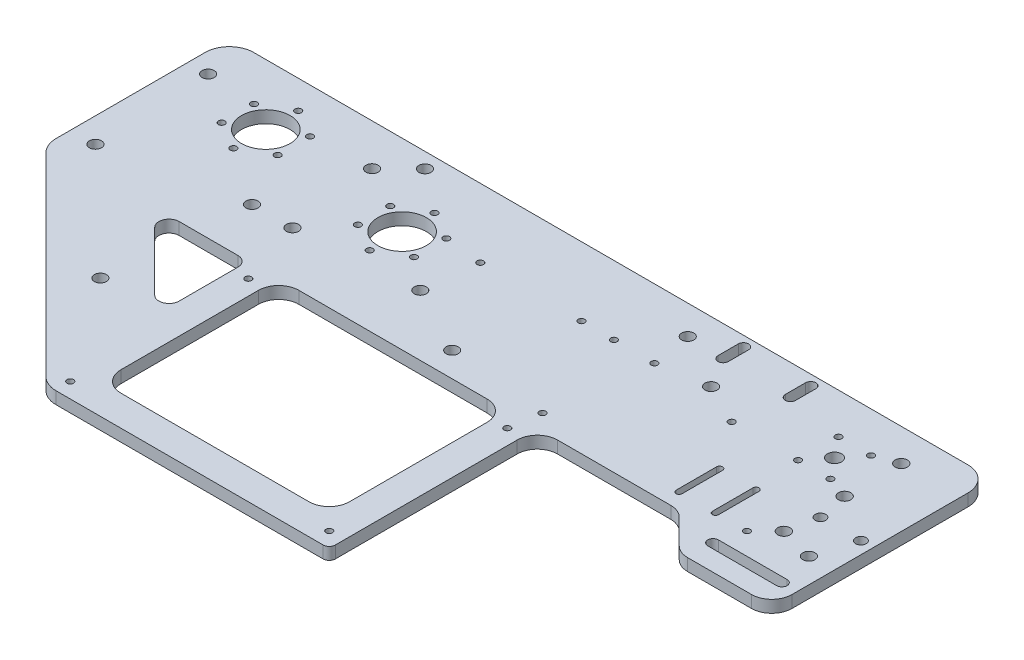
SolidWorks part; units mm, degrees
material "Policarbonato"
ref_plane "Plano frontal" through (0, 0, 0) normal (0, 0, 1) x (1, 0, 0)
ref_plane "Plano superior" through (0, 0, 0) normal (0, 1, 0) x (1, 0, 0)
ref_plane "Plano direito" through (0, 0, 0) normal (1, 0, 0) x (0, 0, -1)
sketch "Esboço1" plane through (0, 0, 0) normal (0, 1, 0) x (1, 0, 0)
  line L3 (-80.5574, -153.6487) -> (51.4721, -153.6487)
  line L4 (54.4721, -150.6487) -> (54.4721, -60.7886)
  line L6 (188.5279, -40.7886) -> (188.5279, 28)
  line L7 (176.5279, 40) -> (-176.5279, 40)
  line L8 (-188.5279, 28) -> (-188.5279, -45.6781)
  line L12 (-122.5768, -50.7886) -> (-93.5279, -50.7886)
  line L13 (-88.5279, -55.7886) -> (-88.5279, -84.8375)
  line L14 (-97.0635, -88.373) -> (-126.1124, -59.3241)
  line L15 (39.4721, -60.6487) -> (39.4721, -128.6487)
  line L16 (29.4721, -138.6487) -> (-63.5279, -138.6487)
  line L17 (-73.5279, -128.6487) -> (-73.5279, -60.6487)
  line L18 (-63.5279, -50.6487) -> (29.4721, -50.6487)
  line L20 (132.5279, 0) -> (148.5279, 0) construction
  line L21 (132.5279, 0) -> (132.5279, 20) construction
  line L22 (132.5279, 20) -> (148.5279, 20) construction
  line L23 (148.5279, 0) -> (148.5279, 20) construction
  line L24 (132.5279, 0) -> (148.5279, 20) construction
  line L25 (132.5279, 20) -> (148.5279, 0) construction
  line L30 (64.4721, -50.7886) -> (178.5279, -50.7886)
  line L31 (134.7221, -43) -> (134.7221, -23) construction
  line L32 (133.2221, -43) -> (133.2221, -23)
  line L33 (136.2221, -43) -> (136.2221, -23)
  line L34 (125.7221, -45.2211) -> (125.7221, -21.4375) construction
  line L36 (116.7221, -43) -> (116.7221, -23) construction
  line L37 (118.2221, -43) -> (118.2221, -23)
  line L38 (115.2221, -43) -> (115.2221, -23)
  line L40 (54.4721, -120.5) -> (144.9721, -120.5) construction
  line L41 (54.4721, -120.5) -> (54.4721, -7) construction
  line L42 (54.4721, -7) -> (144.9721, -7) construction
  line L43 (144.9721, -120.5) -> (144.9721, -7) construction
  line L44 (54.4721, -120.5) -> (144.9721, -7) construction
  line L45 (54.4721, -7) -> (144.9721, -120.5) construction
  line L46 (70.5279, 25) -> (70.5279, 35) construction
  line L47 (67.9779, 25) -> (67.9779, 35)
  line L48 (73.0779, 25) -> (73.0779, 35)
  line L49 (103.7779, 25) -> (103.7779, 35) construction
  line L50 (101.2279, 25) -> (101.2279, 35)
  line L51 (106.3279, 25) -> (106.3279, 35)
  line L52 (-185.0132, -54.1634) -> (-89.0426, -150.134)
  circle A0 centre (-81.0279, -58.1487) radius 1.6
  circle A1 centre (-81.0279, -146.1487) radius 1.6
  circle A2 centre (46.9721, -58.1487) radius 1.6
  circle A3 centre (46.9721, -146.1487) radius 1.6
  circle A8 centre (176.311, -38.4318) radius 3
  circle A9 centre (0, -38.4318) radius 3
  circle A11 centre (-140.5279, 10) radius 12
  circle A20 centre (-140.5279, 10) radius 16 construction
  circle A21 centre (-140.5279, -6) radius 1.6
  circle A22 centre (-154.3843, 2) radius 1.6
  circle A23 centre (-154.3843, 18) radius 1.6
  circle A24 centre (-84.3674, 32.5) radius 3
  circle A25 centre (-176.311, -38.4318) radius 3
  circle A26 centre (140.5279, 10) radius 3.5
  circle A27 centre (148.5279, 0) radius 1.6
  circle A28 centre (148.5279, 20) radius 1.6
  circle A29 centre (132.5279, 0) radius 1.6
  circle A30 centre (132.5279, 20) radius 1.6
  arc A31 (51.4721, -153.6487) -> (54.4721, -150.6487) centre (51.4721, -150.6487) ccw
  arc A34 (188.5279, 28) -> (176.5279, 40) centre (176.5279, 28) ccw
  arc A35 (-176.5279, 40) -> (-188.5279, 28) centre (-176.5279, 28) ccw
  arc A39 (-93.5279, -50.7886) -> (-88.5279, -55.7886) centre (-93.5279, -55.7886) cw
  arc A40 (-88.5279, -84.8375) -> (-97.0635, -88.373) centre (-93.5279, -84.8375) cw
  arc A41 (-126.1124, -59.3241) -> (-122.5768, -50.7886) centre (-122.5768, -55.7886) cw
  arc A42 (39.4721, -128.6487) -> (29.4721, -138.6487) centre (29.4721, -128.6487) cw
  arc A43 (-63.5279, -138.6487) -> (-73.5279, -128.6487) centre (-63.5279, -128.6487) cw
  arc A44 (-73.5279, -60.6487) -> (-63.5279, -50.6487) centre (-63.5279, -60.6487) cw
  arc A45 (29.4721, -50.6487) -> (39.4721, -60.6487) centre (29.4721, -60.6487) cw
  circle A46 centre (-140.5279, 26) radius 1.6
  circle A47 centre (-126.6715, 18) radius 1.6
  circle A48 centre (-126.6715, 2) radius 1.6
  circle A49 centre (-63.1716, 0) radius 16 construction
  circle A50 centre (-63.1716, -16) radius 1.6
  circle A51 centre (-77.028, -8) radius 1.6
  circle A52 centre (-77.028, 8) radius 1.6
  circle A53 centre (-63.1716, 16) radius 1.6
  circle A54 centre (-49.3152, 8) radius 1.6
  circle A55 centre (-49.3152, -8) radius 1.6
  circle A56 centre (-63.1716, 0) radius 12
  circle A57 centre (-33.5279, -20.6487) radius 3
  circle A58 centre (79.5279, 10) radius 3
  arc A62 (188.5279, -40.7886) -> (178.5279, -50.7886) centre (178.5279, -40.7886) cw
  arc A63 (54.4721, -60.7886) -> (64.4721, -50.7886) centre (64.4721, -60.7886) cw
  arc A64 (133.2221, -43) -> (136.2221, -43) centre (134.7221, -43) ccw
  arc A65 (136.2221, -23) -> (133.2221, -23) centre (134.7221, -23) ccw
  arc A66 (118.2221, -43) -> (115.2221, -43) centre (116.7221, -43) cw
  arc A67 (115.2221, -23) -> (118.2221, -23) centre (116.7221, -23) cw
  circle A68 centre (99.7221, 0) radius 1.6
  circle A69 centre (49.2221, -43) radius 1.6
  circle A70 centre (134.7221, -43) radius 1.6 construction
  circle A71 centre (-30.5279, 6) radius 1.6
  circle A72 centre (19.4721, 6) radius 1.6
  circle A73 centre (55.5279, 6) radius 1.6
  circle A75 centre (35.5279, 6) radius 1.6
  circle A76 centre (70.5279, 30) radius 2.55 construction
  circle A77 centre (103.7779, 30) radius 2.55 construction
  circle A78 centre (159.4679, 24.07) radius 3.05
  circle A79 centre (159.4679, -3.93) radius 3.05
  circle A80 centre (159.4679, -33.93) radius 3.05
  arc A81 (67.9779, 25) -> (73.0779, 25) centre (70.5279, 25) ccw
  arc A82 (73.0779, 35) -> (67.9779, 35) centre (70.5279, 35) ccw
  arc A83 (101.2279, 25) -> (106.3279, 25) centre (103.7779, 25) ccw
  arc A84 (106.3279, 35) -> (101.2279, 35) centre (103.7779, 35) ccw
  circle A85 centre (-178.5279, 19.5) radius 3
  circle A86 centre (-97.5279, 19.5) radius 3
  arc A87 (-80.5574, -153.6487) -> (-89.0426, -150.134) centre (-80.5574, -141.6487) cw
  arc A88 (-185.0132, -54.1634) -> (-188.5279, -45.6781) centre (-176.5279, -45.6781) cw
  circle A89 centre (52.3279, 25.68) radius 3
  circle A90 centre (150.2221, -43) radius 1.6
  point P14 (134.7221, -33)
  point P43 (-140.5279, 10)
  point P70 (-144.4721, -50.6487)
  point P82 (-85.5279, -153.6487)
  point P116 (-63.1716, 0)
  point P123 (0, 40)
  point P124 (116.7221, -33)
  point P129 (99.7221, -63.75)
  point P141 (99.7221, -7)
  point P161 (70.5279, 30)
  point P168 (103.7779, 30)
  dimension "D2" = 3
  dimension "D8" = 12
  dimension "D10" = 12
  dimension "D11" = 61
  dimension "D12" = 203.9448
  dimension "D13" = 7.5
  dimension "D14" = 104.1605
  dimension "D16" = 135.7229
  dimension "D20" = 19.68
  dimension "D21" = 3.2
  dimension "D22" = 48.4318
  dimension "D23" = 32
  dimension "D24" = 3.2
  dimension "D25" = 6
  dimension "D26" = 24
  dimension "D27" = 48
  dimension "D28" = 30
  dimension "D29" = 40
  dimension "D30" = 6
  dimension "D34" = 30
  dimension "D31" = 32
  dimension "D32" = 3.2
  dimension "D33" = 24
  dimension "D35" = 6
  dimension "D36" = 155
  dimension "D37" = 30
  dimension "D44" = 7
  dimension "D48" = 10
  dimension "D54" = 50.5
  dimension "D6" = 10
  dimension "D58" = 5
  dimension "D62" = 1.5
  dimension "D72" = 85
  dimension "D75" = 5.1
  dimension "D80" = 14.07
  dimension "D82" = 6.1
  dimension "D83" = 10
  dimension "D19" = 6
  dimension "D47" = 101
  dimension "D1" = 137
  dimension "D9" = 377.0558
  dimension "D15" = 225
  dimension "D17" = 38
  dimension "D18" = 15
  dimension "D38" = 48
  dimension "D39" = 15
  dimension "D40" = 12.2169
  dimension "D41" = 12.2169
  dimension "D42" = 16
  dimension "D43" = 20
  dimension "D45" = 15
  dimension "D46" = 15
  dimension "D49" = 7.5
  dimension "D50" = 7.5
  dimension "D51" = 88
  dimension "D52" = 128
  dimension "D53" = 93
  dimension "D56" = 20.6487
  dimension "D57" = 68
  dimension "D59" = 10
  dimension "D60" = 20.5
  dimension "D61" = 20
  dimension "D63" = 9
  dimension "D64" = 113.5
  dimension "D65" = 90.5
  dimension "D66" = 7
  dimension "D67" = 43
  dimension "D69" = 34
  dimension "D70" = 110
  dimension "D71" = 50
  dimension "D73" = 20
  dimension "D74" = 33.25
  dimension "D76" = 10
  dimension "D77" = 15
  dimension "D78" = 30
  dimension "D79" = 28
  dimension "D81" = 18.94
  dimension "D84" = 81
extrude "Ressalto-extrusão1" add sketch "Esboço1" against normal blind 6
sketch "Esboço2" plane through (0, 0, 0) normal (0, 1, 0) x (1, 0, 0)
  line L0 (188.5279, -40.7886) -> (188.5279, 28) construction
  line L1 (-126.1124, -59.3241) -> (-97.0635, -88.373) construction
  line L2 (-131.2731, -107.9035) -> (-104.403, -81.0335) construction
  line L3 (-185.0132, -54.1634) -> (-89.0426, -150.134) construction
  line L4 (159.4679, -6.98) -> (159.4679, -30.88) construction
  line L5 (-140.5279, 10) -> (-63.1716, 0) construction
  line L6 (176.5279, 40) -> (-176.5279, 40) construction
  line L7 (-91.8498, -25.5) -> (-111.8498, -25.5) construction
  circle A1 centre (-117.8381, -94.4685) radius 3
  arc A2 (-188.5279, -45.6781) -> (-185.0132, -54.1634) centre (-176.5279, -45.6781) ccw construction
  circle A3 centre (182.5279, -18.93) radius 2.6
  circle A4 centre (162.5279, -18.93) radius 2.6
  circle A7 centre (-111.8498, -25.5) radius 3
  circle A8 centre (-91.8498, -25.5) radius 3
  circle A9 centre (159.4679, -3.93) radius 3.05 construction
  circle A10 centre (159.4679, -33.93) radius 3.05 construction
  point P1 (-117.8381, -94.4685)
  point P18 (159.4679, -18.93)
  point P30 (-101.8498, 5)
  point P41 (-101.8498, -25.5)
  dimension "D1" = 76
  dimension "D2" = 6
  dimension "D3" = 20
  dimension "D4" = 5.2
  dimension "D5" = 6
  dimension "D6" = 6
  dimension "D7" = 65.5
  dimension "D8" = 20
extrude "Corte-extrusão1" cut sketch "Esboço2" against normal blind 10
sketch "Esboço3" plane through (0, 0, 0) normal (0, 1, 0) x (1, 0, 0)
  line L0 (142.7858, -68.9886) -> (114.5858, -40.7886)
  line L1 (188.5279, -40.7886) -> (142.7858, -40.7886)
  line L2 (188.5279, -40.7886) -> (188.5279, -68.9886)
  line L3 (188.5279, -68.9886) -> (142.7858, -68.9886)
  line L4 (142.7858, -40.7886) -> (142.7858, -68.9886)
  line L5 (114.5858, -40.7886) -> (142.7858, -40.7886)
  line L6 (180.9279, -56.3886) -> (146.9279, -56.3886) construction
  line L7 (180.9279, -58.9886) -> (146.9279, -58.9886)
  line L8 (180.9279, -53.7886) -> (146.9279, -53.7886)
  line L10 (133.2221, -23) -> (133.2221, -43) construction
  line L11 (136.2221, -43) -> (136.2221, -23) construction
  line L12 (133.2221, -23) -> (133.2221, -43)
  line L13 (136.2221, -43) -> (136.2221, -23)
  line L14 (115.2221, -23) -> (115.2221, -43) construction
  line L15 (118.2221, -43) -> (118.2221, -23) construction
  line L16 (115.2221, -23) -> (115.2221, -43)
  line L17 (118.2221, -43) -> (118.2221, -23)
  line L18 (64.4721, -50.7886) -> (178.5279, -50.7886) construction
  arc A0 (180.9279, -58.9886) -> (180.9279, -53.7886) centre (180.9279, -56.3886) ccw
  arc A1 (146.9279, -53.7886) -> (146.9279, -58.9886) centre (146.9279, -56.3886) ccw
  circle A2 centre (176.311, -38.4318) radius 3 construction
  arc A3 (133.2221, -43) -> (136.2221, -43) centre (134.7221, -43) ccw construction
  circle A4 centre (176.311, -38.4318) radius 3
  arc A5 (133.2221, -43) -> (136.2221, -43) centre (134.7221, -43) ccw
  arc A6 (115.2221, -43) -> (118.2221, -43) centre (116.7221, -43) ccw construction
  arc A7 (115.2221, -43) -> (118.2221, -43) centre (116.7221, -43) ccw
  circle A8 centre (150.2221, -43) radius 1.6 construction
  circle A9 centre (150.2221, -43) radius 1.6
  point P8 (163.9279, -56.3886)
  point P13 (183.5279, -56.3886)
  point P16 (144.3279, -56.3886)
  dimension "D3" = 2.6
  dimension "D1" = 45
  dimension "D2" = 34
  dimension "D4" = 10
  dimension "D5" = 10
  dimension "D6" = 5
  dimension "D7" = 3
extrude "Ressalto-extrusão2" add sketch "Esboço3" against normal up to surface (6 mm away) contours L5 L0 L4 | L1 L4 L3 L2 A1 L8 A0 L7 region at (143.3231, 0, 54.8886) region at (133.6258, 0, 50.5324) up to face at (-117.8381, -6, 91.4685)
fillet "Filete1" radius 10 3 edges at (188.5279, -3, 68.9886) (142.7858, -3, 68.9886) (124.5858, -3, 50.7886)
